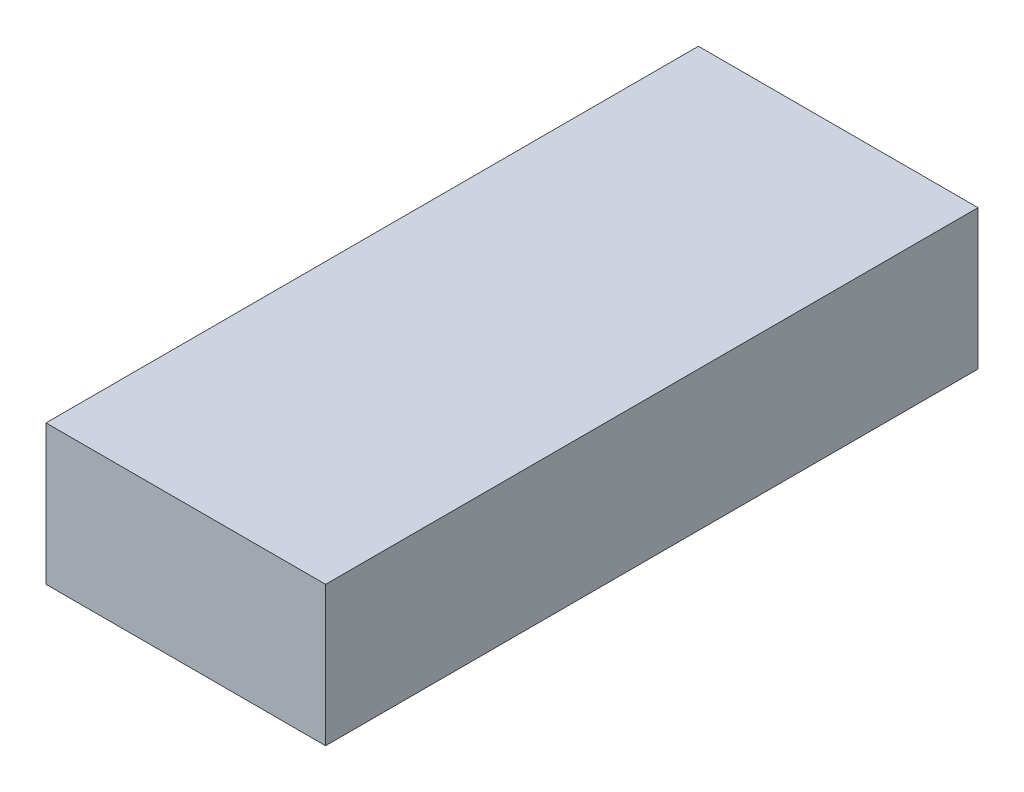
SolidWorks part; units mm, degrees
material "Pine"
ref_plane "Front Plane" through (0, 0, 0) normal (0, 0, 1) x (1, 0, 0)
ref_plane "Top Plane" through (0, 0, 0) normal (0, 1, 0) x (1, 0, 0)
ref_plane "Right Plane" through (0, 0, 0) normal (1, 0, 0) x (0, 0, -1)
sketch "Sketch1" plane through (0, 0, 0) normal (1, 0, 0) x (0, 0, -1)
  line L1 (-44.45, -9.525) -> (44.45, -9.525)
  line L2 (-44.45, -9.525) -> (-44.45, 9.525)
  line L3 (-44.45, 9.525) -> (44.45, 9.525)
  line L4 (44.45, -9.525) -> (44.45, 9.525)
  line L5 (-44.45, -9.525) -> (44.45, 9.525) construction
  line L6 (-44.45, 9.525) -> (44.45, -9.525) construction
  point P0 (0, 0)
  dimension "D1" = 88.9
  dimension "D2" = 19.05
extrude "Boss-Extrude1" add sketch "Sketch1" along normal mid plane 38.1
